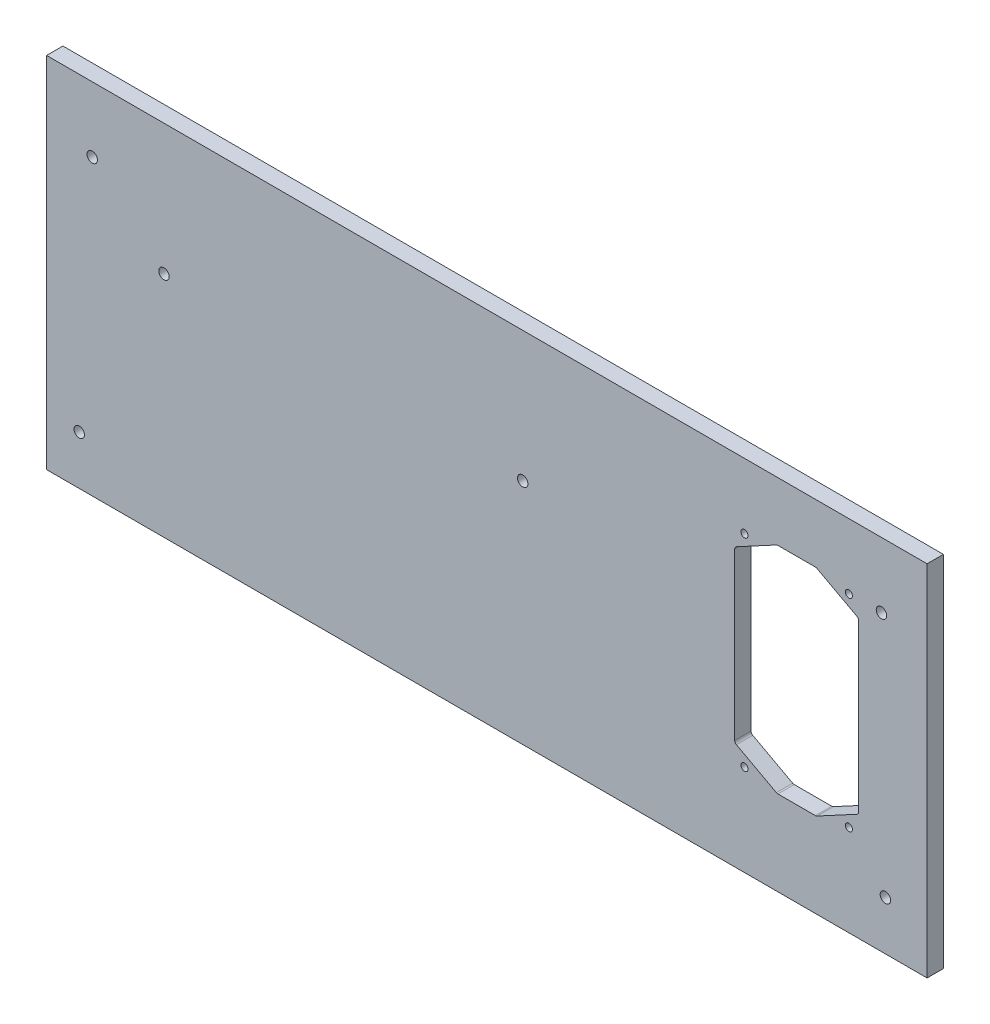
SolidWorks part; units mm, degrees
material "Polycarbonate (PC)"
ref_plane "Front Plane" through (0, 0, 0) normal (0, 0, 1) x (1, 0, 0)
ref_plane "Top Plane" through (0, 0, 0) normal (0, 1, 0) x (1, 0, 0)
ref_plane "Right Plane" through (0, 0, 0) normal (1, 0, 0) x (0, 0, -1)
sketch "Sketch1" plane through (0, 0, 0) normal (0, 0, 1) x (1, 0, 0)
  line L1 (135, -55) -> (-135, -55)
  line L2 (135, -55) -> (135, 55)
  line L3 (135, 55) -> (-135, 55)
  line L4 (-135, -55) -> (-135, 55)
  line L5 (135, -55) -> (-135, 55) construction
  line L6 (135, 55) -> (-135, -55) construction
  point P0 (0, 0)
  dimension "D1" = 110
  dimension "D2" = 270
extrude "Sheet" add sketch "Sketch1" along normal mid plane 5
sketch "Sketch4" plane through (0, 0, -2.5) normal (0, 0, -1) x (-1, 0, 0)
  line L0 (-101, 37) -> (-114, 30)
  line L1 (-89, -29) -> (-101, -29)
  line L2 (-76, -22) -> (-76, 30)
  line L3 (-89, 37) -> (-101, 37)
  line L4 (-114, -22) -> (-114, 30)
  line L5 (-76, -29) -> (-114, 37) construction
  line L6 (-76, 37) -> (-114, -29) construction
  line L7 (-79, -27) -> (-111, -27) construction
  line L8 (-79, -27) -> (-79, 35) construction
  line L9 (-79, 35) -> (-111, 35) construction
  line L10 (-111, -27) -> (-111, 35) construction
  line L11 (-79, -27) -> (-111, 35) construction
  line L12 (-79, 35) -> (-111, -27) construction
  line L13 (-101, -29) -> (-114, -22)
  line L14 (-95, 4) -> (-95, 17.8562) construction
  line L15 (-76, 30) -> (-89, 37)
  line L16 (-76, -22) -> (-89, -29)
  line L17 (-135, -55) -> (-135, 55) construction
  line L18 (135, -55) -> (-135, -55) construction
  circle A0 centre (-79, 35) radius 1.1
  circle A1 centre (-111, 35) radius 1.1
  circle A2 centre (-111, -27) radius 1.1
  circle A3 centre (-79, -27) radius 1.1
  point P0 (-95, 4)
  point P14 (-95, 4)
  dimension "D1" = 2.2
  dimension "D2" = 62
  dimension "D3" = 32
  dimension "D4" = 38
  dimension "D5" = 66
  dimension "D6" = 13
  dimension "D7" = 7
  dimension "D8" = 13
  dimension "D9" = 7
  dimension "D10" = 7
  dimension "D11" = 13
  dimension "D12" = 13
  dimension "D13" = 7
  dimension "D14" = 40
  dimension "D15" = 59
extrude "Cut-Extrude1" cut sketch "Sketch4" against normal through all
fillet "Fillet1" radius 1 8 edges at (76, 30, 0) (89, -29, 0) (101, -29, 0) (114, -22, 0) (114, 30, 0) (101, 37, 0) (89, 37, 0) (76, -22, 0)
hole_wizard "Ø3.2 (3.2) MountHoles" positions "Sketch5" profile "Sketch6" hole size "Ø3.2" standard "ANSI Metric" end condition through all
sketch "Sketch5" plane through (0, 0, -2.5) normal (0, 0, -1) x (-1, 0, 0)
  line L0 (135, -55) -> (-135, -55) construction
  line L1 (135, 55) -> (135, -55) construction
  line L2 (-135, 55) -> (135, 55) construction
  line L3 (-135, -55) -> (-135, 55) construction
  point P0 (-121, 35)
  point P2 (-122.2168, -40)
  point P4 (125, -40)
  point P6 (121, 35)
  dimension "D1" = 15
  dimension "D2" = 10
  dimension "D3" = 20
  dimension "D4" = 14
  dimension "D5" = 14
sketch "Sketch6" plane through (121, 35, -2.5) normal (1, 0, 0) x (0, 1, 0)
  line L0 (0, 0) -> (0, 5)
  line L1 (0, 5) -> (1.6, 5)
  line L2 (1.6, 5) -> (1.6, 1.65)
  line L3 (1.6, 1.65) -> (3.25, 0)
  line L5 (3.25, 0) -> (0, 0)
  line L6 (-1.6, 1.65) -> (-3.25, 0) construction
  line L11 (0, -6.35) -> (0, 107.95) construction
  dimension "Thru Hole Dia." = 3.2
  dimension "Thru Hole Depth" = 5
  dimension "Near C'Sink Dia." = 6.5
  dimension "Near C'Sink Angle" = 90
hole_wizard "Ø3.2 (3.2) MiddlePartHoles" positions "Sketch7" profile "Sketch8" hole size "Ø3.2" standard "ANSI Metric" end condition through all
sketch "Sketch7" plane through (0, 0, -2.5) normal (0, 0, -1) x (-1, 0, 0)
  line L0 (135, 55) -> (135, -55) construction
  line L1 (-135, 55) -> (135, 55) construction
  point P0 (-11, 15)
  point P2 (99, 15)
  dimension "D1" = 36
  dimension "D2" = 110
  dimension "D3" = 40
sketch "Sketch8" plane through (11, 15, -2.5) normal (1, 0, 0) x (0, 1, 0)
  line L0 (0, 0) -> (0, 5)
  line L1 (0, 5) -> (1.6, 5)
  line L2 (1.6, 5) -> (1.6, 1.65)
  line L3 (1.6, 1.65) -> (3.25, 0)
  line L5 (3.25, 0) -> (0, 0)
  line L6 (-1.6, 1.65) -> (-3.25, 0) construction
  line L11 (0, -6.35) -> (0, 107.95) construction
  dimension "Thru Hole Dia." = 3.2
  dimension "Thru Hole Depth" = 5
  dimension "Near C'Sink Dia." = 6.5
  dimension "Near C'Sink Angle" = 90
equation "\"D5@Sketch5\"=\"D4@Sketch5\""
